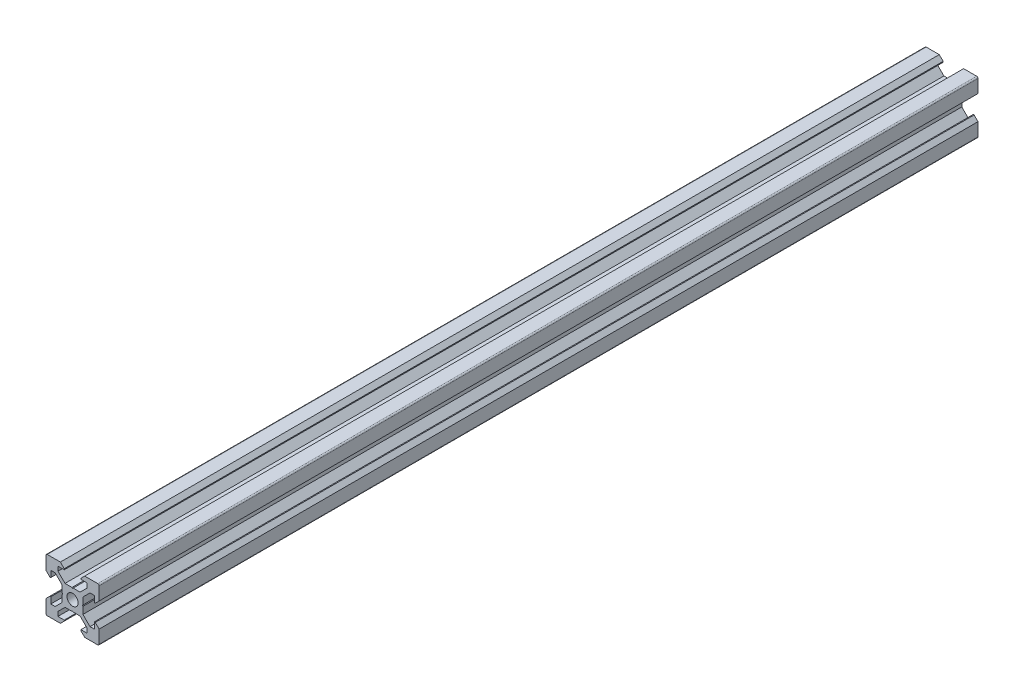
SolidWorks part; units mm, degrees
material "6061-T6 (SS)"
ref_plane "Front Plane" through (0, 0, 0) normal (0, 0, 1) x (1, 0, 0)
ref_plane "Top Plane" through (0, 0, 0) normal (0, 1, 0) x (1, 0, 0)
ref_plane "Right Plane" through (0, 0, 0) normal (1, 0, 0) x (0, 0, -1)
sketch "Sketch1" plane through (0, 0, 0) normal (0, 0, 1) x (1, 0, 0)
  line L1 (9.5, -10) -> (-9.5, -10)
  line L2 (10, -9.5) -> (10, 9.5)
  line L3 (9.5, 10) -> (-9.5, 10)
  line L4 (-10, -9.5) -> (-10, 9.5)
  line L5 (10, -10) -> (-10, 10) construction
  line L6 (10, 10) -> (-10, -10) construction
  circle A0 centre (0, 0) radius 2.1
  arc A1 (-9.5, 10) -> (-10, 9.5) centre (-9.5, 9.5) ccw
  arc A2 (10, 9.5) -> (9.5, 10) centre (9.5, 9.5) ccw
  arc A3 (9.5, -10) -> (10, -9.5) centre (9.5, -9.5) ccw
  arc A4 (-9.5, -10) -> (-10, -9.5) centre (-9.5, -9.5) cw
  point P0 (0, 0)
  line B0 (0, 0) -> (0, 10) construction
  line B1 (0, 3.69) -> (-0.21, 3.9)
  line B2 (-0.21, 3.9) -> (-2.8393, 3.9)
  line B3 (-2.8393, 3.9) -> (-5.5, 6.5607)
  line B4 (-5.5, 6.5607) -> (-5.5, 8.2)
  line B5 (-5.5, 8.2) -> (-3.125, 8.2)
  line B6 (-3.125, 8.2) -> (-3.125, 8.545)
  line B7 (-3.125, 8.545) -> (-4.58, 10)
  line B8 (-4.58, 10) -> (4.58, 10)
  line B9 (0, 0) -> (-5.9132, 5.9132) construction
  line B10 (3.125, 8.545) -> (4.58, 10)
  line B11 (3.125, 8.2) -> (3.125, 8.545)
  line B12 (5.5, 8.2) -> (3.125, 8.2)
  line B13 (5.5, 6.5607) -> (5.5, 8.2)
  line B14 (2.8393, 3.9) -> (5.5, 6.5607)
  line B15 (0.21, 3.9) -> (2.8393, 3.9)
  line B16 (0, 3.69) -> (0.21, 3.9)
  line B17 (0, 0) -> (-10, 0) construction
  line B18 (-3.69, 0) -> (-3.9, -0.21)
  line B19 (-3.9, -0.21) -> (-3.9, -2.8393)
  line B20 (-3.9, -2.8393) -> (-6.5607, -5.5)
  line B21 (-6.5607, -5.5) -> (-8.2, -5.5)
  line B22 (-8.2, -5.5) -> (-8.2, -3.125)
  line B23 (-8.2, -3.125) -> (-8.545, -3.125)
  line B24 (-8.545, -3.125) -> (-10, -4.58)
  line B25 (-10, -4.58) -> (-10, 4.58)
  line B26 (0, 0) -> (-5.9132, -5.9132) construction
  line B27 (-8.545, 3.125) -> (-10, 4.58)
  line B28 (-8.2, 3.125) -> (-8.545, 3.125)
  line B29 (-8.2, 5.5) -> (-8.2, 3.125)
  line B30 (-6.5607, 5.5) -> (-8.2, 5.5)
  line B31 (-3.9, 2.8393) -> (-6.5607, 5.5)
  line B32 (-3.9, 0.21) -> (-3.9, 2.8393)
  line B33 (-3.69, 0) -> (-3.9, 0.21)
  line B34 (0, 0) -> (0, -10) construction
  line B35 (0, -3.69) -> (0.21, -3.9)
  line B36 (0.21, -3.9) -> (2.8393, -3.9)
  line B37 (2.8393, -3.9) -> (5.5, -6.5607)
  line B38 (5.5, -6.5607) -> (5.5, -8.2)
  line B39 (5.5, -8.2) -> (3.125, -8.2)
  line B40 (3.125, -8.2) -> (3.125, -8.545)
  line B41 (3.125, -8.545) -> (4.58, -10)
  line B42 (4.58, -10) -> (-4.58, -10)
  line B43 (0, 0) -> (5.9132, -5.9132) construction
  line B44 (-3.125, -8.545) -> (-4.58, -10)
  line B45 (-3.125, -8.2) -> (-3.125, -8.545)
  line B46 (-5.5, -8.2) -> (-3.125, -8.2)
  line B47 (-5.5, -6.5607) -> (-5.5, -8.2)
  line B48 (-2.8393, -3.9) -> (-5.5, -6.5607)
  line B49 (-0.21, -3.9) -> (-2.8393, -3.9)
  line B50 (0, -3.69) -> (-0.21, -3.9)
  line B51 (0, 0) -> (10, 0) construction
  line B52 (3.69, 0) -> (3.9, 0.21)
  line B53 (3.9, 0.21) -> (3.9, 2.8393)
  line B54 (3.9, 2.8393) -> (6.5607, 5.5)
  line B55 (6.5607, 5.5) -> (8.2, 5.5)
  line B56 (8.2, 5.5) -> (8.2, 3.125)
  line B57 (8.2, 3.125) -> (8.545, 3.125)
  line B58 (8.545, 3.125) -> (10, 4.58)
  line B59 (10, 4.58) -> (10, -4.58)
  line B60 (0, 0) -> (5.9132, 5.9132) construction
  line B61 (8.545, -3.125) -> (10, -4.58)
  line B62 (8.2, -3.125) -> (8.545, -3.125)
  line B63 (8.2, -5.5) -> (8.2, -3.125)
  line B64 (6.5607, -5.5) -> (8.2, -5.5)
  line B65 (3.9, -2.8393) -> (6.5607, -5.5)
  line B66 (3.9, -0.21) -> (3.9, -2.8393)
  line B67 (3.69, 0) -> (3.9, -0.21)
  dimension "D1" = 4.2
  dimension "D3" = 0.5
  dimension "D2" = 20
sketch_block_instance "V Slot 1-4"
sketch_block "V Slot 1" parameters "D1"=10, "D2"=11, "D3"=4.3, "D4"=1.8, "D5"=0.21, "D6"=45, "D7"=9.16, "D8"=1.5, "D9"=6.25
sketch_block_instance "V Slot 1-5"
sketch_block_instance "V Slot 1-6"
sketch_block_instance "V Slot 1-7"
extrude "Boss-Extrude1" add sketch "Sketch1" along normal blind 331 contours B67 B52 B53 B54 B55 B56 B57 B58 L2 A2 L3 B10 B11 B12 B13 B14 B15 B16 B1 B2 B3 B4 B5 B6 B7 A1 L4 B27 B28 B29 B30 B31 B32 B33 B18 B19 B20 B21 B22 B23 B24 A4 L1 B44 B45 B46 B47 B48 B49 region at (7.04, -9.7172, 0)
